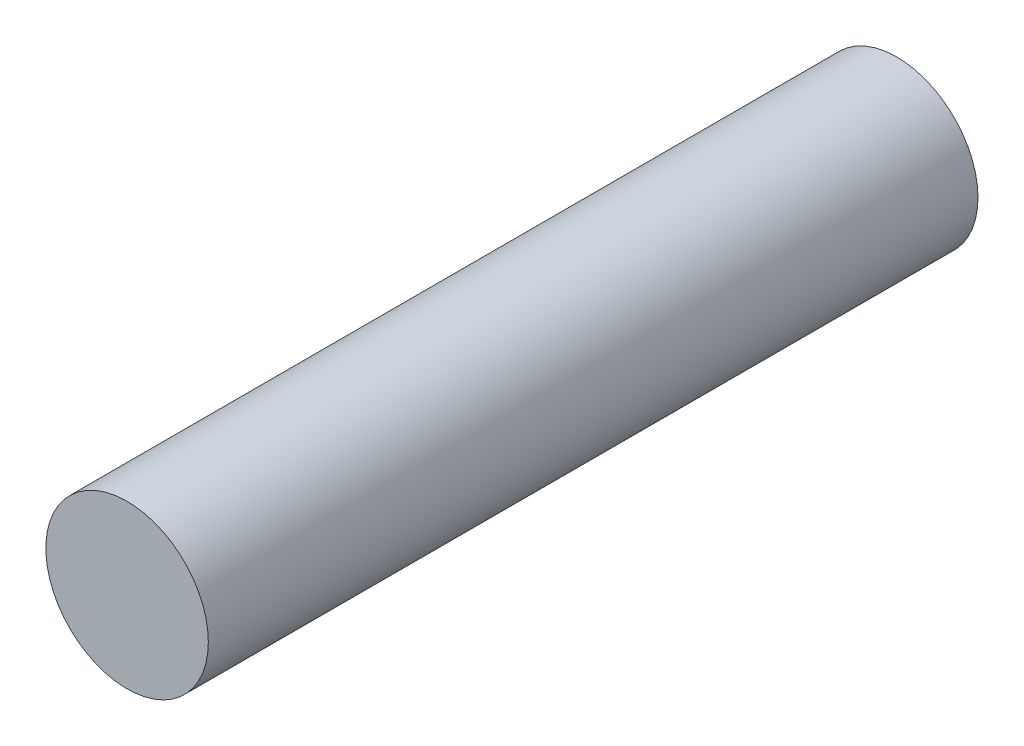
SolidWorks part; units mm, degrees
ref_plane "Front Plane" through (0, 0, 0) normal (0, 0, 1) x (1, 0, 0)
ref_plane "Top Plane" through (0, 0, 0) normal (0, 1, 0) x (1, 0, 0)
ref_plane "Right Plane" through (0, 0, 0) normal (1, 0, 0) x (0, 0, -1)
sketch "Sketch1" plane through (0, 0, 0) normal (0, 0, 1) x (1, 0, 0)
  circle A0 centre (0, 0) radius 24.13
  dimension "D1" = 48.26
extrude "Boss-Extrude1" add sketch "Sketch1" along normal blind 228.6
